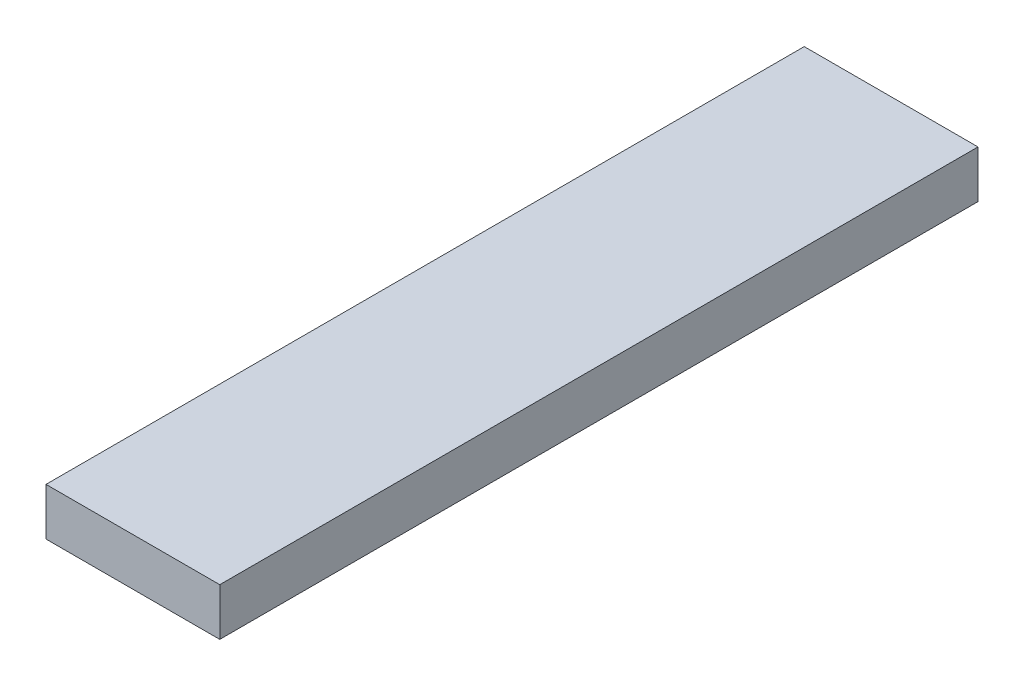
SolidWorks part; units mm, degrees
material "Cedar"
ref_plane "Front Plane" through (0, 0, 0) normal (0, 0, 1) x (1, 0, 0)
ref_plane "Top Plane" through (0, 0, 0) normal (0, 1, 0) x (1, 0, 0)
ref_plane "Right Plane" through (0, 0, 0) normal (1, 0, 0) x (0, 0, -1)
sketch "Sketch1" plane through (0, 0, 0) normal (0, 0, 1) x (1, 0, 0)
  line L1 (-69.85, -19.05) -> (69.85, -19.05)
  line L2 (-69.85, -19.05) -> (-69.85, 19.05)
  line L3 (-69.85, 19.05) -> (69.85, 19.05)
  line L4 (69.85, -19.05) -> (69.85, 19.05)
  line L5 (-69.85, -19.05) -> (69.85, 19.05) construction
  line L6 (-69.85, 19.05) -> (69.85, -19.05) construction
  point P0 (0, 0)
  dimension "D1" = 139.7
  dimension "D2" = 38.1
extrude "Boss-Extrude1" add sketch "Sketch1" along normal blind 304.8 and the other way blind 304.8
